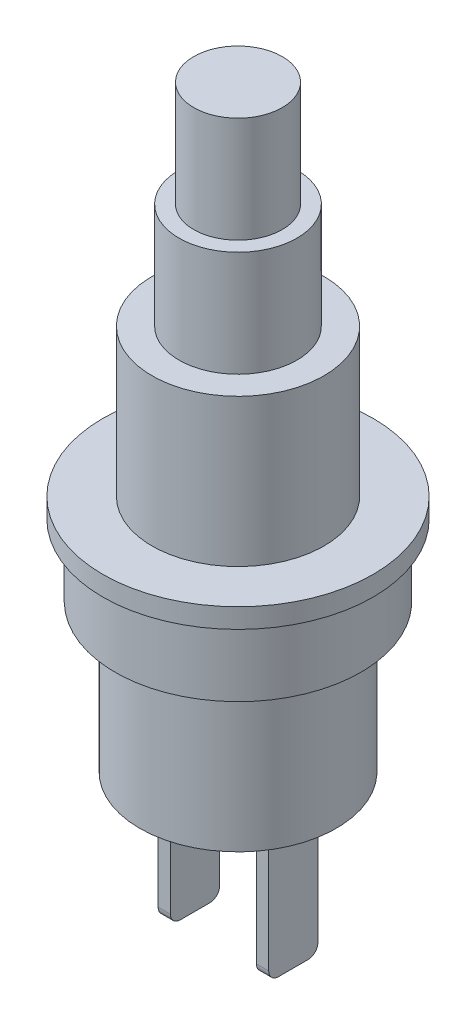
SolidWorks part; units mm, degrees
ref_plane "Plan de face" through (0, 0, 0) normal (0, 0, 1) x (1, 0, 0)
ref_plane "Plan de dessus" through (0, 0, 0) normal (0, 1, 0) x (1, 0, 0)
ref_plane "Plan de droite" through (0, 0, 0) normal (1, 0, 0) x (0, 0, -1)
sketch "Esquisse1" plane through (0, 0, 0) normal (0, 0, 1) x (1, 0, 0)
  line L0 (0, 0) -> (0, 24.3)
  line L1 (0, 24.3) -> (-1.8, 24.3)
  line L2 (-1.8, 24.3) -> (-1.8, 20)
  line L3 (-1.8, 20) -> (-2.4, 20)
  line L4 (-2.4, 20) -> (-2.4, 15.7)
  line L5 (-2.4, 15.7) -> (-3.5, 15.7)
  line L6 (-3.5, 15.7) -> (-3.5, 9.7)
  line L7 (-3.5, 9.7) -> (-5.5, 9.7)
  line L8 (-5.5, 9.7) -> (-5.5, 8.9)
  line L9 (-5.5, 8.9) -> (-5, 8.9)
  line L10 (-5, 8.9) -> (-5, 6)
  line L11 (-5, 6) -> (-4, 6)
  line L12 (-4, 6) -> (-4, 0)
  line L13 (-4, 0) -> (0, 0)
  dimension "D2" = 8.9
  dimension "D3" = 8.6
  dimension "D4" = 4
  dimension "D5" = 3.5
  dimension "D6" = 1
  dimension "D7" = 0.5
  dimension "D8" = 1.8
  dimension "D9" = 2.4
  dimension "D10" = 4.3
  dimension "D11" = 0.8
  dimension "D12" = 14.6
  dimension "D13" = 6
  dimension "D14" = 2.9
revolve "Révolution1" add sketch "Esquisse1" angle 360 about L0
sketch "Esquisse2" plane through (0, 0, 0) normal (0, 0, 1) x (1, 0, 0)
  line L0 (-2.25, 0) -> (-1.75, 0)
  line L1 (-4, 0) -> (4, 0) construction
  line L2 (-1.75, 0) -> (-1.75, -5.8)
  line L3 (-2.25, 0) -> (-2.25, -5.8)
  line L4 (-2.25, -5.8) -> (-1.75, -5.8)
  line L5 (0, 0) -> (0, -5.6723) construction
  line L6 (2.25, 0) -> (1.75, 0)
  line L7 (2.25, 0) -> (2.25, -5.8)
  line L8 (2.25, -5.8) -> (1.75, -5.8)
  line L9 (1.75, 0) -> (1.75, -5.8)
  point P5 (-2, 0)
  dimension "D1" = 0.5
  dimension "D2" = 5.8
  dimension "D3" = 2
extrude "Boss.-Extru.1" add sketch "Esquisse2" along normal blind 1 and the other way blind 1
fillet "Congé2" radius 0.4 4 edges at (2, -5.8, 1) (-2, -5.8, -1) (-2, -5.8, 1) (2, -5.8, -1)
